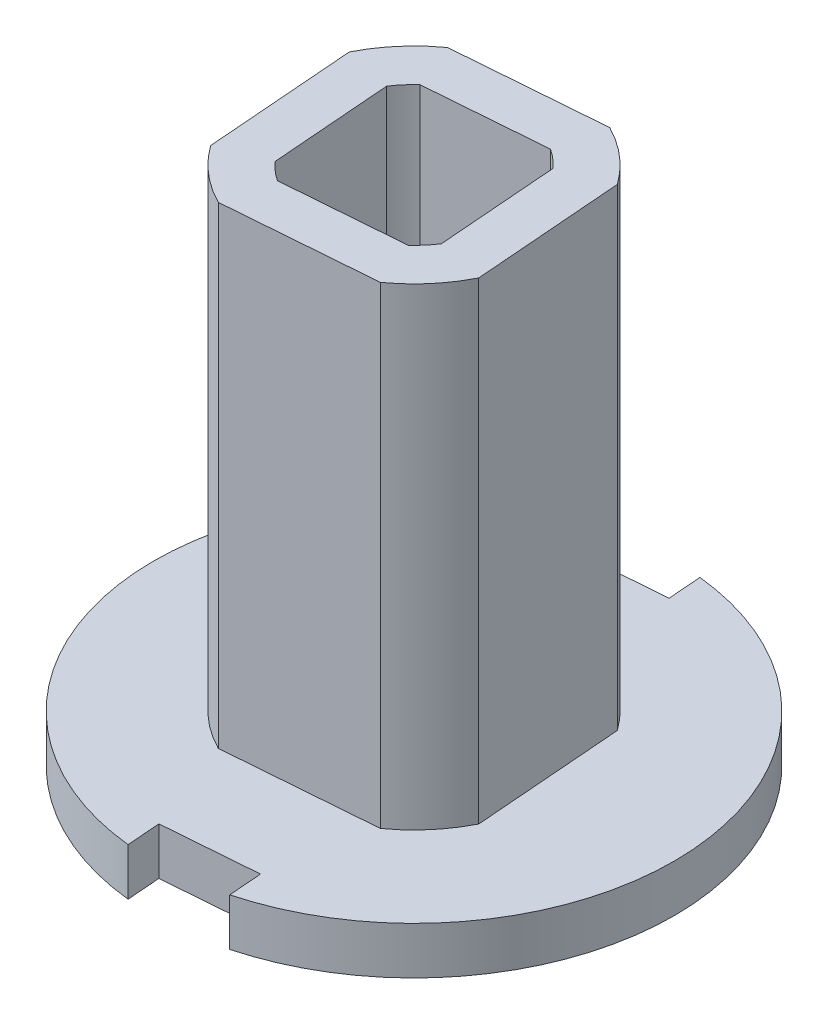
SolidWorks part; units mm, degrees
ref_plane "Front Plane" through (0, 0, 0) normal (0, 0, 1) x (1, 0, 0)
ref_plane "Top Plane" through (0, 0, 0) normal (0, 1, 0) x (1, 0, 0)
ref_plane "Right Plane" through (0, 0, 0) normal (1, 0, 0) x (0, 0, -1)
sketch "Sketch1" plane through (0, 125.9948, 0) normal (0, -1, 0) x (1, 0, 0.0028)
  line L38 (-1.8018, -2.5005) -> (1.3768, -2.7574)
  line L39 (2.5005, -1.8018) -> (2.6289, -0.2125)
  line L40 (2.6289, -0.2125) -> (2.7574, 1.3768)
  line L41 (1.8018, 2.5005) -> (-1.3768, 2.7574)
  line L42 (-2.5005, 1.8018) -> (-2.6289, 0.2125)
  line L43 (-2.6289, 0.2125) -> (-2.7574, -1.3768)
  line L44 (1.6322, -0.1319) -> (1.7358, 1.1497)
  line L45 (1.4136, 1.5286) -> (-1.1497, 1.7358)
  line L46 (-1.5286, 1.4136) -> (-1.6322, 0.1319)
  line L47 (-1.6322, 0.1319) -> (-1.7358, -1.1497)
  line L48 (-1.4136, -1.5286) -> (1.1497, -1.7358)
  line L49 (1.5286, -1.4136) -> (1.6322, -0.1319)
  line L50 (1.6322, -0.1319) -> (1.7358, 1.1497)
  line L51 (1.4136, 1.5286) -> (-1.1497, 1.7358)
  line L52 (-1.5286, 1.4136) -> (-1.6322, 0.1319)
  line L53 (-1.6322, 0.1319) -> (-1.7358, -1.1497)
  line L54 (-1.4136, -1.5286) -> (1.1497, -1.7358)
  line L55 (1.5286, -1.4136) -> (1.6322, -0.1319)
  line L56 (0.4431, 5.4821) -> (-0.4431, -5.4821) construction
  line L57 (-0.561, 5.4713) -> (-0.6181, 4.7653)
  line L58 (-0.6181, 4.7653) -> (1.3754, 4.6042)
  line L59 (1.4325, 5.3102) -> (1.3754, 4.6042)
  line L60 (0, 0) -> (2.6289, -0.2125) construction
  line L61 (-1.4325, -5.3102) -> (-1.3754, -4.6042)
  line L62 (-1.3754, -4.6042) -> (0.6181, -4.7653)
  line L63 (0.561, -5.4713) -> (0.6181, -4.7653)
  circle A27 centre (0, 0) radius 5.5
  arc A28 (1.3768, -2.7574) -> (2.5005, -1.8018) centre (0, 0) ccw
  arc A29 (2.7574, 1.3768) -> (1.8018, 2.5005) centre (0, 0) ccw
  arc A30 (-1.3768, 2.7574) -> (-2.5005, 1.8018) centre (0, 0) ccw
  arc A31 (1.7358, 1.1497) -> (1.4136, 1.5286) centre (0, 0) ccw
  arc A32 (-1.1497, 1.7358) -> (-1.5286, 1.4136) centre (0, 0) ccw
  arc A33 (-1.7358, -1.1497) -> (-1.4136, -1.5286) centre (0, 0) ccw
  arc A34 (1.1497, -1.7358) -> (1.5286, -1.4136) centre (0, 0) ccw
  arc A35 (1.7358, 1.1497) -> (1.4136, 1.5286) centre (0, 0) ccw
  arc A36 (-1.1497, 1.7358) -> (-1.5286, 1.4136) centre (0, 0) ccw
  arc A37 (-1.7358, -1.1497) -> (-1.4136, -1.5286) centre (0, 0) ccw
  arc A38 (1.1497, -1.7358) -> (1.5286, -1.4136) centre (0, 0) ccw
  arc A39 (-2.7574, -1.3768) -> (-1.8018, -2.5005) centre (0, 0) ccw
  point P22 (0.3787, 4.6847)
  arc M12 (1.241, -0.1003) -> (-1.241, 0.1003) centre (0, 0) ccw
  arc M13 (-1.241, 0.1003) -> (1.241, -0.1003) centre (0, 0) ccw
  dimension "D2" = 11
  dimension "D4" = 0.8
  dimension "D5" = 2
  dimension "D1" = 0.05
  dimension "D3" = 1
extrude "Boss-Extrude1" add sketch "Sketch1" along normal blind 1 contours L63 A27 L59 L58 L57 L61 L62 A39 L43 L42 A30 L41 A29 L40 L39 A28 L38 | L43 A39 L38 A28 L39 L40 A29 L41 A30 L42 A38 L54 A37 L53 L52 A36 L51 A35 L50 L55 | L54 A38 L55 L50 A35 L51 A36 L52 L53 A37 M12 M13 | M13 M12 region at (-2.2829, 125.9948, -1.9525) region at (1.5336, 125.9948, -0.7645) region at (-0.7585, 125.9948, 5.1287) region at (0, 125.9948, 0)
extrude "Boss-Extrude2" add sketch "Sketch1<4>" against normal blind 10 contours L43 A39 L38 A28 L39 L40 A29 L41 A30 L42 A38 L54 A37 L53 L52 A36 L51 A35 L50 L55 region at (-2.2829, 125.9948, -1.9525)
sketch "Sketch1<4>" plane through (0, 125.9948, 0) normal (0, -1, 0) x (1, 0, 0.0028) same geometry as "Sketch1"
